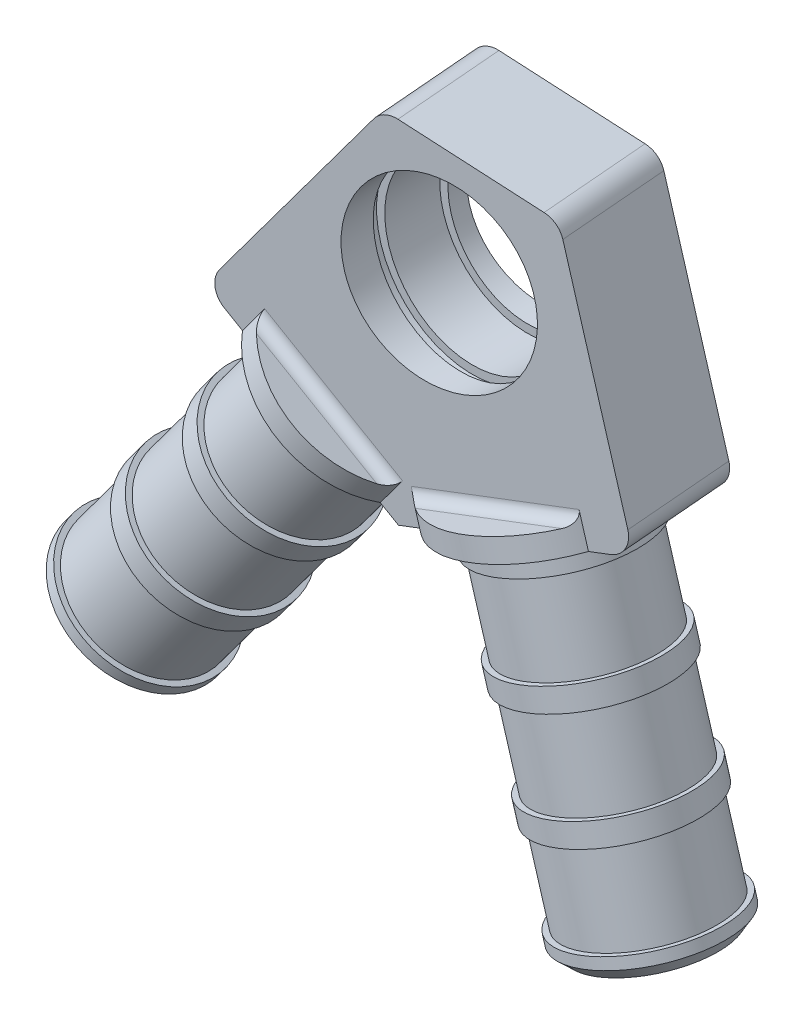
SolidWorks part; units mm, degrees
material "7075-T6 (SN)"
ref_plane "Front Plane" through (0, 0, 0) normal (0, 0, 1) x (1, 0, 0)
ref_plane "Top Plane" through (0, 0, 0) normal (0, 1, 0) x (1, 0, 0)
ref_plane "Right Plane" through (0, 0, 0) normal (1, 0, 0) x (0, 0, -1)
sketch3d "04e FSus"
  line L0 (-536.5, 150, 117) -> (-427, 581, 127)
  line L1 (-427, 581, 127) -> (-236, 150, 142)
  line L2 (-236, 150, 142) -> (-536.5, 150, 117)
  line L3 (-578, 235, 280) -> (-416, 556, 332)
  line L4 (-416, 556, 332) -> (-236, 235, 280)
  line L5 (-236, 235, 280) -> (-578, 235, 280)
  line L6 (-427, 542, 156) -> (-427, 383, 405)
  line L7 (-490, 573, 155) -> (-490, 200, 151)
  line L9 (-427, 352, 446) -> (-427, 210.5, 587.5)
  line L10 (-490, 573, 155) -> (-420, 543.5, 235)
  line L11 (-420, 543.5, 235) -> (-420, 600, 235)
  line L22 (-420, -543.5, 235) -> (-420, -600, 235)
  line L23 (-490, -573, 155) -> (-420, -543.5, 235)
  line L24 (-427, -352, 446) -> (-427, -210.5, 587.5)
  line L26 (-490, -573, 155) -> (-490, -200, 151)
  line L27 (-427, -542, 156) -> (-427, -383, 405)
  line L28 (-236, -235, 280) -> (-578, -235, 280)
  line L29 (-416, -556, 332) -> (-236, -235, 280)
  line L30 (-578, -235, 280) -> (-416, -556, 332)
  line L31 (-236, -150, 142) -> (-536.5, -150, 117)
  line L32 (-427, -581, 127) -> (-236, -150, 142)
  line L33 (-536.5, -150, 117) -> (-427, -581, 127)
  line L34 (-427, 352, 446) -> (-427, 255, 425)
  line L35 (-427, 255, 425) -> (-427, 383, 405)
  line L36 (-427, -352, 446) -> (-427, -255, 425)
  line L37 (-427, -255, 425) -> (-427, -383, 405)
  circle A0 centre (-420, 600, 235) radius 235
  circle A1 centre (-420, -600, 235) radius 235
  point P0 (-536.5, 150, 117)
  point P1 (-236, 150, 142)
  point P2 (-427, 581, 127)
  point P6 (-578, 235, 280)
  point P7 (-236, 235, 280)
  point P8 (-416, 556, 332)
  point P12 (-427, 542, 156)
  point P13 (-427, 383, 405)
  point P16 (-490, 573, 155)
  point P17 (-490, 200, 151)
  point P20 (-427, 210.5, 587.5)
  point P21 (-427, 352, 446)
  point P24 (-420, 543.5, 235)
  point P25 (-420, 543.5, 235)
  point P26 (-420, 600, 235)
  point P34 (-420, 834.8568, 243.2014)
  point P37 (-420, -834.8568, 243.2014)
ref_plane "Plane1" through (-420, 0, 0) normal (1, 0, 0) x (0, 0, -1)
sketch3d "04e RSus"
  line L0 (973.5, -295, 172) -> (1268, -255, 139)
  line L1 (1268, -255, 139) -> (1172, -574, 138)
  line L2 (1172, -574, 138) -> (973.5, -295, 172)
  line L3 (975, -295, 295) -> (1275, -255, 270)
  line L4 (1275, -255, 270) -> (1187, -567.5, 312.5)
  line L5 (1187, -567.5, 312.5) -> (975, -295, 295)
  line L6 (1185.5, -499, 282) -> (1221.5, -332, 80.5)
  line L7 (1282, -534, 222.5) -> (1271, -255, 207.5)
  line L10 (1282, -534, 222.5) -> (1180, -535, 235)
  line L11 (1180, -535, 235) -> (1180, -600, 235)
  line L22 (1180, 535, 235) -> (1180, 600, 235)
  line L23 (1282, 534, 222.5) -> (1180, 535, 235)
  line L26 (1282, 534, 222.5) -> (1271, 255, 207.5)
  line L27 (1185.5, 499, 282) -> (1221.5, 332, 80.5)
  line L28 (1187, 567.5, 312.5) -> (975, 295, 295)
  line L29 (1275, 255, 270) -> (1187, 567.5, 312.5)
  line L30 (975, 295, 295) -> (1275, 255, 270)
  line L31 (1172, 574, 138) -> (973.5, 295, 172)
  line L32 (1268, 255, 139) -> (1172, 574, 138)
  line L33 (973.5, 295, 172) -> (1268, 255, 139)
  line L36 (968.3812, -335.5468, 84.7795) -> (1166.5155, -352.9385, 105.7642)
  line L37 (1166.5155, -352.9385, 105.7642) -> (1171.9664, -327.6521, 75.2538)
  line L38 (1171.9664, -327.6521, 75.2538) -> (1221.5, -332, 80.5)
  line L39 (968.3812, 335.5468, 84.7795) -> (1166.5155, 352.9385, 105.7642)
  line L40 (1166.5155, 352.9385, 105.7642) -> (1171.9664, 327.6521, 75.2538)
  line L41 (1171.9664, 327.6521, 75.2538) -> (1221.5, 332, 80.5)
  circle A0 centre (1180, -600, 235) radius 235
  circle A1 centre (1180, 600, 235) radius 235
  point P0 (973.5, -295, 172)
  point P1 (1268, -255, 139)
  point P2 (1172, -574, 138)
  point P6 (975, -295, 295)
  point P7 (1275, -255, 270)
  point P8 (1187, -567.5, 312.5)
  point P12 (968.3812, -335.5468, 84.7795)
  point P13 (1185.5, -499, 282)
  point P14 (1221.5, -332, 80.5)
  point P15 (1282, -534, 222.5)
  point P16 (1271, -255, 207.5)
  point P21 (1166.5155, -352.9385, 105.7642)
  point P22 (1171.9664, -327.6521, 75.2538)
  point P24 (1180, -535, 235)
  point P25 (1180, -600, 235)
  point P34 (1180, 365, 235)
  point P38 (1180, -365, 235)
ref_plane "Plane2" through (1180, 0, 0) normal (1, 0, 0) x (0, 0, -1)
ref_plane "Plane3" through (0, -600, 0) normal (0, 1, 0) x (1, 0, 0)
ref_plane "Plane4" through (0, 0, 235) normal (0, 0, -1) x (-1, 0, 0)
ref_plane "lower A-arm" through (34.3657, 11.2607, 293.039) normal (-0.1164, -0.0381, -0.9925) x (-0.9932, 0.0045, 0.1163)
sketch "草图17" plane through (34.3657, 11.2607, 293.039) normal (-0.1164, -0.0381, -0.9925) x (-0.9932, 0.0045, 0.1163)
  line L0 (-1125.8355, 559.7702) -> (-1142.116, 548.1536)
  line L1 (-1142.116, 548.1536) -> (-1161.2557, 553.9565)
  line L2 (-1145.4191, 568.2776) -> (-945.5607, 288.1778) construction
  line L3 (-1242.076, 249.4745) -> (-1145.4191, 568.2776) construction
  line L4 (-1125.8355, 559.7702) -> (-1139.7754, 579.3068)
  line L5 (-1139.7754, 579.3068) -> (-1154.2922, 576.9241)
  line L6 (-1154.2922, 576.9241) -> (-1161.2557, 553.9565)
extrude "凸台-拉伸1" add sketch "草图17" along normal blind 5 and the other way blind 5.5
sketch "草图22" plane through (-55.6734, 184.9982, -0.5799) normal (0.2882, -0.9576, 0.003) x (0.9576, 0.2882, -0.0009)
  circle A0 centre (1287.5676, 139.7987) radius 6.5
  point P0 (1287.5676, 139.7987)
extrude "凸台-拉伸2" add sketch "草图22" along normal blind 31
sketch "草图23" plane through (640.098, 899.6844, -109.639) normal (-0.5769, -0.8108, 0.0988) x (0.8168, -0.5726, 0.0698)
  circle A0 centre (638.2553, 206.4227) radius 6.5
  point P0 (638.2553, 206.4227)
extrude "凸台-拉伸3" add sketch "草图23" along normal blind 31
fillet "圆角3" radius 2 4 edges at (1180.8419, 582.6099, 136.8841) (1166.4238, 585.0558, 138.481) (1187.7581, 559.6282, 136.9562) (1152.5786, 565.5959, 140.8525)
sketch "草图27" plane through (-55.6734, 184.9982, -0.5799) normal (0.2882, -0.9576, 0.003) x (0.9576, 0.2882, -0.0009)
  circle A0 centre (1287.5676, 139.7987) radius 7
  point P0 (1287.5676, 139.7987)
ref_plane "基准面1" through (-52.8878, 175.7417, -0.5509) normal (0.2882, -0.9576, 0.003) x (-0.9576, -0.2882, 0.0009)
ref_plane "基准面2" through (-50.1021, 166.4851, -0.5219) normal (0.2882, -0.9576, 0.003) x (-0.9576, -0.2882, 0.0009)
extrude "凸台-拉伸5" add sketch "草图27" along normal blind 2 from surface starting at plane "基准面1"
extrude "凸台-拉伸6" add sketch "草图27<2>" along normal blind 2 from surface starting at plane "基准面2"
sketch "草图27<2>" plane through (-55.6734, 184.9982, -0.5799) normal (0.2882, -0.9576, 0.003) x (0.9576, 0.2882, -0.0009) same geometry as "草图27"
extrude "凸台-拉伸7" add sketch "草图27<3>" along normal blind 2
sketch "草图27<3>" plane through (-55.6734, 184.9982, -0.5799) normal (0.2882, -0.9576, 0.003) x (0.9576, 0.2882, -0.0009) same geometry as "草图27"
extrude "凸台-拉伸8" add sketch "草图27<4>" against normal blind 2 from surface starting at face at (1192.4312, 528.6647, 138.148)
sketch "草图27<4>" plane through (-55.6734, 184.9982, -0.5799) normal (0.2882, -0.9576, 0.003) x (0.9576, 0.2882, -0.0009) same geometry as "草图27"
sketch "草图28" plane through (640.098, 899.6844, -109.639) normal (-0.5769, -0.8108, 0.0988) x (0.8168, -0.5726, 0.0698)
  circle A0 centre (638.2553, 206.4227) radius 7
  point P0 (638.2553, 206.4227)
extrude "凸台-拉伸9" add sketch "草图28" along normal blind 2
extrude "凸台-拉伸10" add sketch "草图28<2>" against normal blind 2 from surface starting at face at (1148.8561, 530.2579, 142.8714)
sketch "草图28<2>" plane through (640.098, 899.6844, -109.639) normal (-0.5769, -0.8108, 0.0988) x (0.8168, -0.5726, 0.0698) same geometry as "草图28"
ref_plane "基准面3" through (634.5215, 891.8463, -108.6838) normal (-0.5769, -0.8108, 0.0988) x (-0.8168, 0.5726, -0.0698)
ref_plane "基准面4" through (628.945, 884.0083, -107.7286) normal (-0.5769, -0.8108, 0.0988) x (-0.8168, 0.5726, -0.0698)
extrude "凸台-拉伸11" add sketch "草图28<3>" along normal blind 2 from surface starting at plane "基准面3"
sketch "草图28<3>" plane through (640.098, 899.6844, -109.639) normal (-0.5769, -0.8108, 0.0988) x (0.8168, -0.5726, 0.0698) same geometry as "草图28"
extrude "凸台-拉伸12" add sketch "草图28<4>" along normal blind 2 from surface starting at plane "基准面4"
sketch "草图28<4>" plane through (640.098, 899.6844, -109.639) normal (-0.5769, -0.8108, 0.0988) x (0.8168, -0.5726, 0.0698) same geometry as "草图28"
sketch "草图29" plane through (640.098, 899.6844, -109.639) normal (-0.5769, -0.8108, 0.0988) x (0.8168, -0.5726, 0.0698)
  circle A0 centre (638.2553, 206.4227) radius 9
  point P0 (638.2553, 206.4227)
extrude "凸台-拉伸13" add sketch "草图29" against normal blind 2
sketch "草图30" plane through (-55.6734, 184.9982, -0.5799) normal (0.2882, -0.9576, 0.003) x (0.9576, 0.2882, -0.0009)
  circle A0 centre (1287.5676, 139.7987) radius 9
  point P0 (1287.5676, 139.7987)
extrude "凸台-拉伸14" add sketch "草图30" against normal blind 2
sketch "草图34" plane through (34.3657, 11.2607, 293.039) normal (-0.1164, -0.0381, -0.9925) x (-0.9932, 0.0045, 0.1163)
  line L0 (-1145.4191, 568.2776) -> (-945.5607, 288.1778) construction
  line L1 (-1140.4881, 549.3152) -> (-1129.0917, 557.4468) construction
  line L8 (-1111.147, 527.9931) -> (-1114.8101, 525.3794)
  line L9 (-1114.8101, 525.3794) -> (-1131.8858, 549.3108)
  line L11 (-937.5414, 284.6864) -> (-1147.0706, 578.3398)
  line L12 (-1248.4047, 244.1103) -> (-937.5414, 284.6864)
  line L13 (-1147.0706, 578.3398) -> (-1248.4047, 244.1103)
  line L14 (-1111.147, 527.9931) -> (-1125.6098, 548.2627)
  arc A1 (-1125.6098, 548.2627) -> (-1131.8858, 549.3108) centre (-1129.2721, 545.6477) ccw
  point P0 (-1131.8858, 549.3108)
  dimension "D2" = 4.5
  dimension "D1" = 5
revolve "切除-旋转1" cut sketch "草图34" angle 360 about L31
sketch "草图35" plane through (34.3657, 11.2607, 293.039) normal (-0.1164, -0.0381, -0.9925) x (-0.9932, 0.0045, 0.1163)
  line L0 (-1242.076, 249.4745) -> (-1145.4191, 568.2776) construction
  line L1 (-1157.4276, 552.7959) -> (-1144.0298, 548.7338) construction
  line L5 (-1165.4169, 517.8283) -> (-1161.1105, 516.5226)
  line L6 (-1161.1105, 516.5226) -> (-1152.1795, 545.9799)
  line L8 (-1147.0706, 578.3398) -> (-1248.4047, 244.1103)
  line L9 (-937.5414, 284.6864) -> (-1147.0706, 578.3398)
  line L10 (-1248.4047, 244.1103) -> (-937.5414, 284.6864)
  line L11 (-1157.7915, 542.9792) -> (-1165.4169, 517.8283)
  arc A1 (-1157.7915, 542.9792) -> (-1152.1795, 545.9799) centre (-1153.4851, 541.6735) cw
  point P0 (-1152.1795, 545.9799)
  dimension "D1" = 5
  dimension "D2" = 4.5
revolve "切除-旋转2" cut sketch "草图35" angle 360 about L32
ref_axis "基准轴1" through (1168.6524, 553.4585, 139.2364) along (0.1606, 0.9852, -0.0593)
ref_plane "horizon" through (0, 0, 138) normal (0, 0, 1) x (1, 0, 0)
sketch "草图39" plane through (0, 0, 138) normal (0, 0, 1) x (1, 0, 0)
  circle A0 centre (1172, 574) radius 7.25
extrude "切除-拉伸4" cut sketch "草图39" against normal blind 7 and the other way blind 7
sketch "草图40" plane through (0, 0, 138) normal (0, 0, 1) x (1, 0, 0)
  circle A0 centre (1172, 574) radius 8
extrude "切除-拉伸5" cut sketch "草图40" along normal blind 7 and the other way blind 2.5
sketch "草图41" plane through (0, 0, 138) normal (0, 0, 1) x (1, 0, 0)
  circle A0 centre (1172, 574) radius 8.75
extrude "切除-拉伸6" cut sketch "草图41" along normal blind 1.05 from offset 2.5
fillet "圆角5" radius 1 4 edges at (1162.0149, 560.5928, 134.6483) (1176.1153, 558.2009, 133.0866) (1163.237, 560.9932, 145.0692) (1177.3374, 558.6013, 143.5075)
chamfer "Chamfer1" distance 1 angle 45 2 edges at (1149.2635, 529.9681, 142.8714) (1192.91, 528.8088, 138.148)
